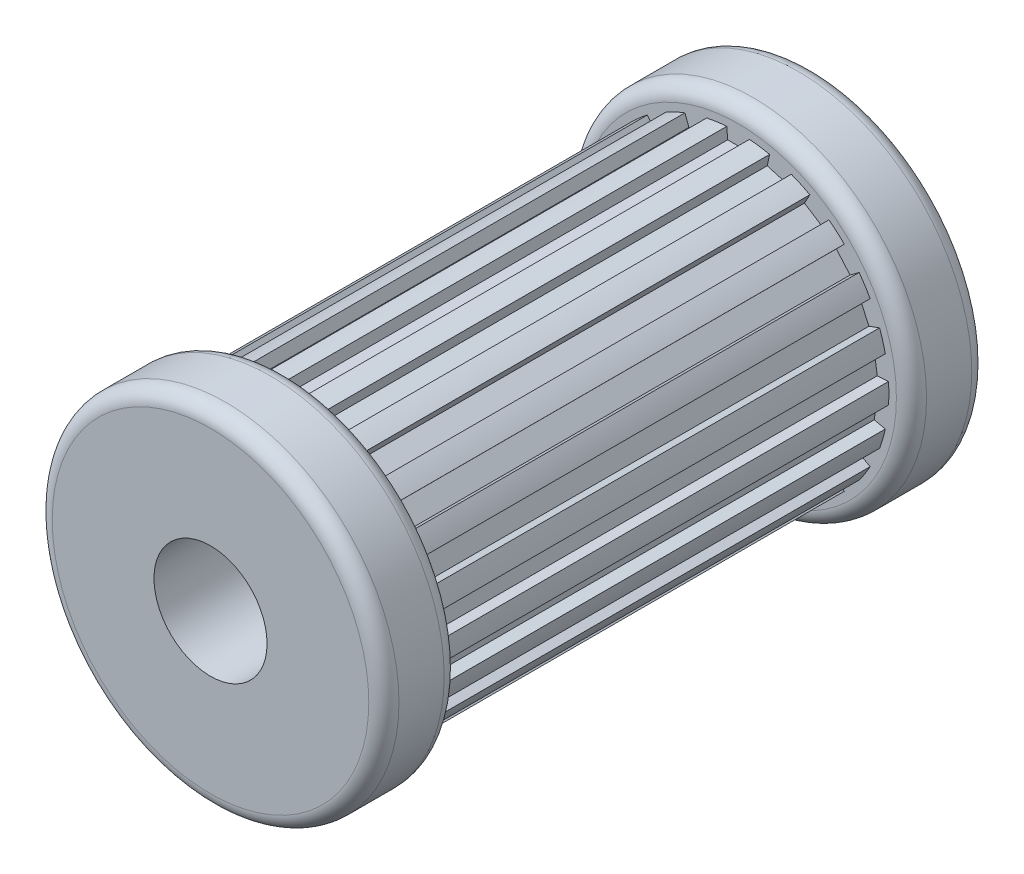
SolidWorks part; units mm, degrees
ref_plane "Front Plane" through (0, 0, 0) normal (0, 0, 1) x (1, 0, 0)
ref_plane "Top Plane" through (0, 0, 0) normal (0, 1, 0) x (1, 0, 0)
ref_plane "Right Plane" through (0, 0, 0) normal (1, 0, 0) x (0, 0, -1)
sketch "Sketch1" plane through (0, 0, 0) normal (0, 0, 1) x (1, 0, 0)
  circle A0 centre (0, 0) radius 20
  dimension "D1" = 40
extrude "Boss-Extrude1" add sketch "Sketch1" along normal mid plane 70
sketch "Sketch2" plane through (0, 0, 35) normal (0, 0, 1) x (1, 0, 0)
  line L0 (0, 0) -> (0, 20) construction
  line L1 (0, 0) -> (1.5, 19.9437)
  line L2 (-1.3875, 18.4479) -> (1.3875, 18.4479)
  line L3 (0, 0) -> (-1.5, 19.9437)
  circle A0 centre (0, 0) radius 20 construction
  circle A2 centre (0, 0) radius 20
  circle A3 centre (0, 0) radius 20
  point P13 (0, 18.4479)
  circle M5 centre (0, 0) radius 20
  dimension "D2" = 3
  dimension "D3" = 1.5
  dimension "D1" = 0
extrude "Cut-Extrude1" cut sketch "Sketch2" against normal through all contours L0 L2 L1 M5 | L2 L0 A3 L3 region at (-0.7182, 19.2248, 35) region at (0.7182, 19.2248, 35)
pattern_circular "CirPattern1" count 22 over 360 about axis through (0, 0, 35) along (0, 0, -1) of "Cut-Extrude1"
sketch "Sketch3" plane through (0, 0, 35) normal (0, 0, 1) x (1, 0, 0)
  circle A0 centre (0, 0) radius 23
  arc A1 (-1.5, 19.9437) -> (-4.1795, 19.5584) centre (0, 0) ccw construction
  dimension "D1" = 3
extrude "Boss-Extrude2" add sketch "Sketch3" against normal blind 10
extrude "Boss-Extrude3" add sketch "Sketch3<2>" against normal blind 10 from vertex starting at point (18.7645, 6.9204, -35)
sketch "Sketch3<2>" plane through (0, 0, 35) normal (0, 0, 1) x (1, 0, 0) same geometry as "Sketch3"
sketch "Sketch4" plane through (0, 0, 35) normal (0, 0, 1) x (1, 0, 0)
  circle A0 centre (0, 0) radius 7.5
  dimension "D1" = 15
extrude "Cut-Extrude2" cut sketch "Sketch4" against normal through all
fillet "Fillet2" radius 2 4 edges at (23, 0, -35) (23, 0, -45) (23, 0, 25) (23, 0, 35)
